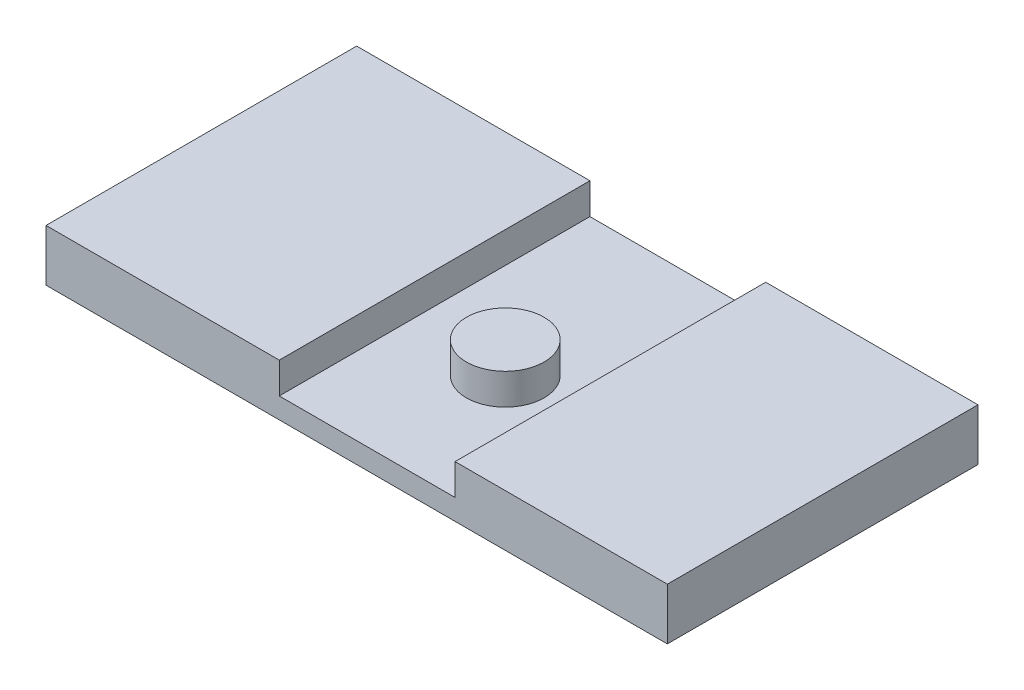
SolidWorks part; units mm, degrees
ref_plane "Front Plane" through (0, 0, 0) normal (0, 0, 1) x (1, 0, 0)
ref_plane "Top Plane" through (0, 0, 0) normal (0, 1, 0) x (1, 0, 0)
ref_plane "Right Plane" through (0, 0, 0) normal (1, 0, 0) x (0, 0, -1)
sketch "Sketch1" plane through (0, 0, 0) normal (0, 1, 0) x (1, 0, 0)
  line L1 (-152.4, -76.2) -> (152.4, -76.2)
  line L2 (-152.4, -76.2) -> (-152.4, 76.2)
  line L3 (-152.4, 76.2) -> (152.4, 76.2)
  line L4 (152.4, -76.2) -> (152.4, 76.2)
  line L5 (-152.4, -76.2) -> (152.4, 76.2) construction
  line L6 (-152.4, 76.2) -> (152.4, -76.2) construction
  point P0 (0, 0)
  dimension "D1" = 152.4
  dimension "D2" = 304.8
extrude "Boss-Extrude1" add sketch "Sketch1" along normal blind 25.4
sketch "Sketch2" plane through (0, 25.4, 0) normal (0, 1, 0) x (-1, 0, 0)
  line L0 (-152.4, -76.2) -> (152.4, -76.2) construction
  line L1 (37.973, -76.2) -> (-48.26, -76.2)
  line L2 (37.973, -76.2) -> (37.973, 76.2)
  line L3 (37.973, 76.2) -> (-48.26, 76.2)
  line L4 (-48.26, -76.2) -> (-48.26, 76.2)
  point P0 (0, 0)
  dimension "D1" = 152.4
  dimension "D2" = 37.973
  dimension "D3" = 48.26
extrude "Cut-Extrude1" cut sketch "Sketch2" against normal blind 15.24
sketch "Sketch3" plane through (0, 10.16, 0) normal (0, 1, 0) x (-1, 0, 0)
  line L0 (37.973, 76.2) -> (-48.26, 76.2) construction
  circle A0 centre (-8.763, 12.065) radius 19.05
  dimension "D1" = 38.1
  dimension "D2" = 64.135
  dimension "D3" = 46.736
extrude "Boss-Extrude2" add sketch "Sketch3" along normal up to surface (15.24 mm away) up to face at (100.33, 25.4, 0)
sketch "Sketch4" plane through (0, 10.16, 0) normal (0, 1, 0) x (1, 0, 0)
  circle A0 centre (8.763, -12.065) radius 19.685
  circle A1 centre (8.763, -12.065) radius 19.05 construction
  dimension "D1" = 39.37
